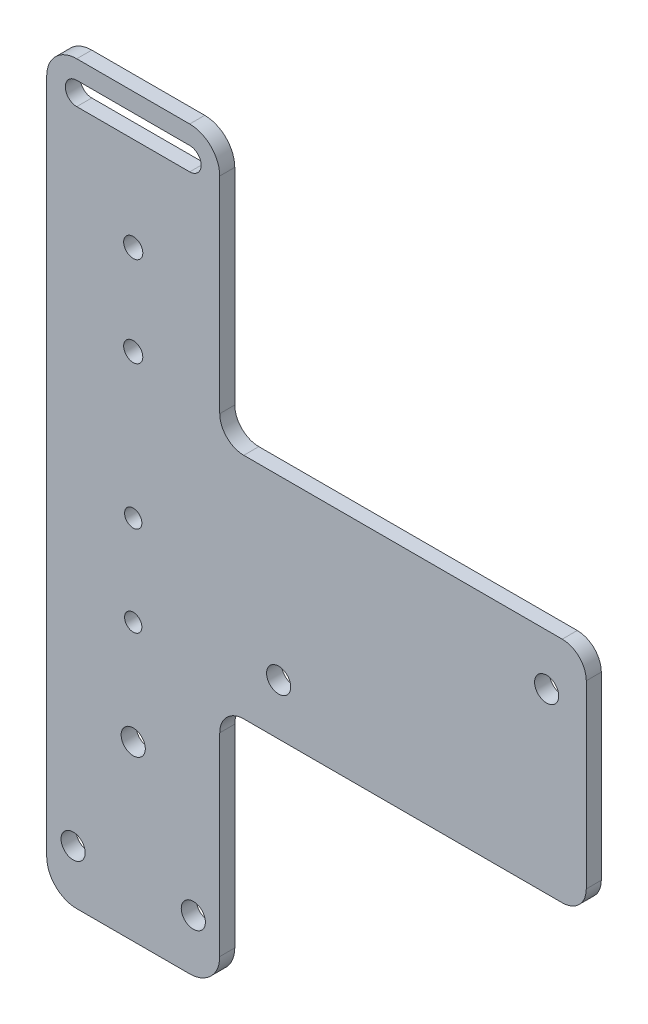
SolidWorks part; units mm, degrees
ref_plane "Front Plane" through (0, 0, 0) normal (0, 0, 1) x (1, 0, 0)
ref_plane "Top Plane" through (0, 0, 0) normal (0, 1, 0) x (1, 0, 0)
ref_plane "Right Plane" through (0, 0, 0) normal (1, 0, 0) x (0, 0, -1)
ref_plane "Plane1" through (0, 0, 1.5875) normal (0, 0, 1) x (1, 0, 0)
sketch "Sketch1" plane through (0, 0, 1.5875) normal (0, 0, 1) x (1, 0, 0)
  line L6 (-11.938, 80.2005) -> (11.938, 80.2005)
  line L7 (11.938, 75.3745) -> (-11.938, 75.3745)
  line L8 (18.288, -65.0875) -> (18.288, -24.13)
  line L9 (23.368, -19.05) -> (90.678, -19.05)
  line L10 (95.758, -13.97) -> (95.758, 24.13)
  line L11 (90.678, 29.21) -> (23.368, 29.21)
  line L12 (18.288, 34.29) -> (18.288, 77.7875)
  line L13 (11.938, 84.1375) -> (-11.938, 84.1375)
  line L14 (-18.288, 77.7875) -> (-18.288, -65.0875)
  line L15 (-11.938, -71.4375) -> (11.938, -71.4375)
  circle A8 centre (87.376, 18.415) radius 2.5527
  circle A9 centre (30.734, -8.255) radius 2.5527
  arc A10 (-11.938, 75.3745) -> (-11.938, 80.2005) centre (-11.938, 77.7875) cw
  arc A11 (11.938, 80.2005) -> (11.938, 75.3745) centre (11.938, 77.7875) cw
  circle A12 centre (0, -13.0175) radius 1.8288
  circle A13 centre (0, 6.0325) radius 1.8288
  circle A14 centre (0, 36.5125) radius 2.0193
  circle A15 centre (0, 55.5625) radius 2.0193
  arc A16 (18.288, -24.13) -> (23.368, -19.05) centre (23.368, -24.13) cw
  arc A17 (90.678, -19.05) -> (95.758, -13.97) centre (90.678, -13.97) ccw
  arc A18 (95.758, 24.13) -> (90.678, 29.21) centre (90.678, 24.13) ccw
  arc A19 (23.368, 29.21) -> (18.288, 34.29) centre (23.368, 34.29) cw
  arc A20 (18.288, 77.7875) -> (11.938, 84.1375) centre (11.938, 77.7875) ccw
  arc A21 (-11.938, 84.1375) -> (-18.288, 77.7875) centre (-11.938, 77.7875) ccw
  arc A22 (-18.288, -65.0875) -> (-11.938, -71.4375) centre (-11.938, -65.0875) ccw
  arc A23 (11.938, -71.4375) -> (18.288, -65.0875) centre (11.938, -65.0875) ccw
  circle A40 centre (12.7, -60.325) radius 2.5527
  circle A41 centre (-12.7, -60.325) radius 2.5527
  circle A42 centre (0, -34.925) radius 2.5527
extrude "Boss-Extrude1" add sketch "Sketch1" against normal blind 3.175
